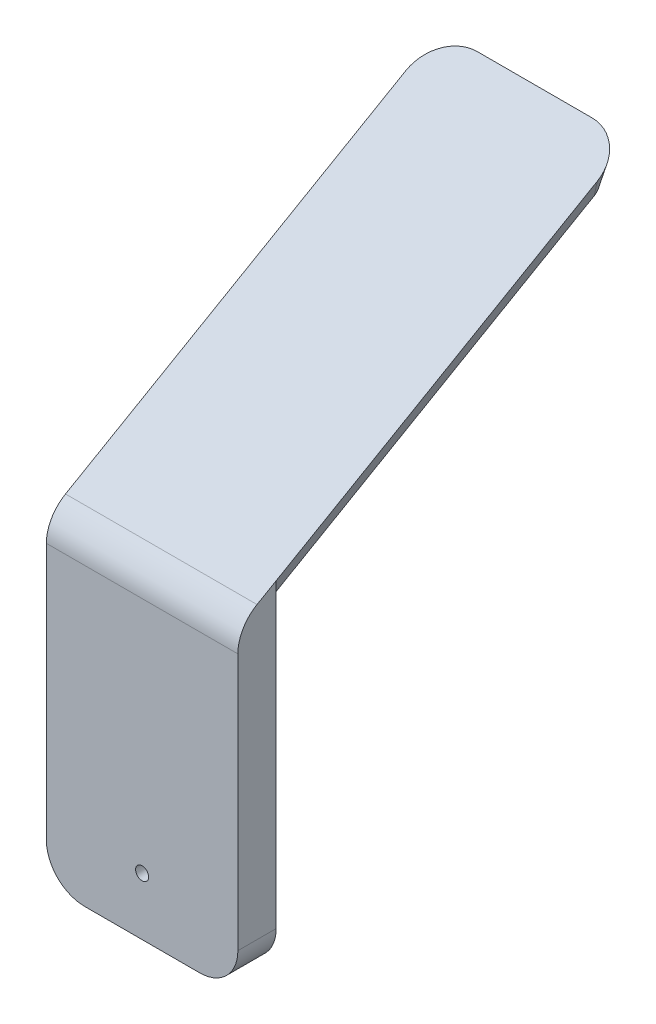
SolidWorks part; units mm, degrees
ref_plane "Front Plane" through (0, 0, 0) normal (1, 0, 0) x (0, 1, 0)
ref_plane "Top Plane" through (0, 0, 0) normal (0, 0, 1) x (0, 1, 0)
ref_plane "Right Plane" through (0, 0, 0) normal (0, 1, 0) x (-1, 0, 0)
sketch "Sketch2" plane through (0, 0, 0) normal (1, 0, 0) x (0, 1, 0)
  line L0 (0, 0) -> (80, 0)
  line L1 (80, 0) -> (137.735, -100)
  line L2 (283.7298, -100) -> (-8.2598, -100) construction
  point P3 (137.735, -100)
  point P8 (137.735, -100)
  dimension "D1" = 80
  dimension "D2" = 60
  dimension "D3" = 100
extrude "Extrude-Thin1" add sketch "Sketch2" along normal blind 50 thin thin type mid plane wall 10
fillet "Fillet2" radius 10 2 edges at (0, 0, 0) (50, 0, 0)
fillet "Fillet3" radius 10 1 edges at (25, 82.8868, 5)
sketch "Sketch3" plane through (0, 0, 0) normal (0, 0, 1) x (0, 1, 0)
  line L0 (0, -25) -> (30, -25) construction
  line L1 (0, -40) -> (0, -10) construction
  circle A0 centre (15, -25) radius 1.7
  dimension "D1" = 15
  dimension "D2" = 3.4
extrude "Cut-Extrude1" cut sketch "Sketch3" against normal up to next and the other way through all
fillet "Fillet9" radius 10 2 edges at (50, 137.735, -100) (0, 137.735, -100)
chamfer "Chamfer1" distance 10 angle 30 5 edges at (0, 102.7591, -49.4199) (50, 102.7591, -49.4199) (2.9289, 131.9404, -99.9635) (25, 133.4049, -102.5) (47.0711, 131.9404, -99.9635) first distance on face at (0, 75.1628, -25.9313) first distance on face at (50, 75.1628, -25.9313) first distance on face at (3.9645, 135.7528, -96.5667) first distance on face at (25, 137.735, -100) first distance on face at (46.0355, 135.7528, -96.5667)
